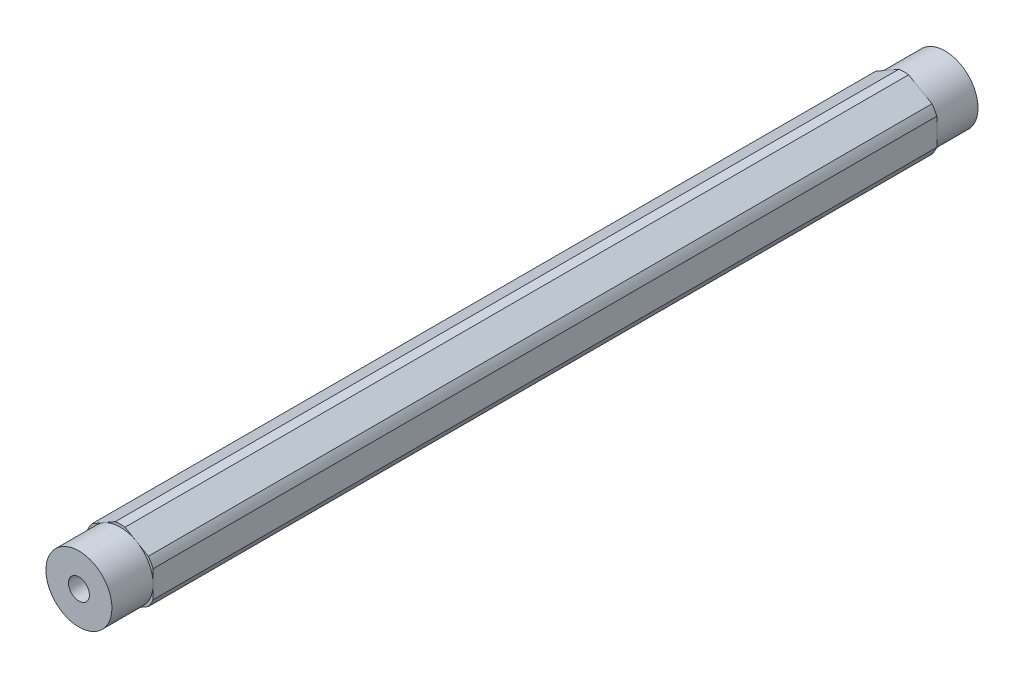
SolidWorks part; units mm, degrees
ref_plane "Front Plane" through (0, 0, 0) normal (0, 0, 1) x (1, 0, 0)
ref_plane "Top Plane" through (0, 0, 0) normal (0, 1, 0) x (1, 0, 0)
ref_plane "Right Plane" through (0, 0, 0) normal (1, 0, 0) x (0, 0, -1)
sketch "Sketch1" plane through (0, 0, 0) normal (0, 0, 1) x (1, 0, 0)
  line L1 (0, 7.3323) -> (-6.35, 3.6662)
  line L2 (-6.35, 3.6662) -> (-6.35, -3.6662)
  line L3 (-6.35, -3.6662) -> (0, -7.3323)
  line L4 (0, -7.3323) -> (6.35, -3.6662)
  line L5 (6.35, -3.6662) -> (6.35, 3.6662)
  line L6 (6.35, 3.6662) -> (0, 7.3323)
  circle A0 centre (0, 0) radius 6.35 construction
  circle A1 centre (0, 0) radius 6.858
  circle A2 centre (0, 0) radius 2.0193
  dimension "D1" = 12.7
  dimension "D2" = 13.716
  dimension "D3" = 4.0386
extrude "Boss-Extrude1" add sketch "Sketch1" along normal mid plane 150.8125 contours L5 A1 L6 L1 L2 L3 L4 region at (0, 6.6711, 0)
sketch "Sketch2" plane through (0, 0, 75.4062) normal (0, 0, 1) x (1, 0, 0)
  circle A0 centre (0, 0) radius 6.35
  circle A1 centre (0, 0) radius 2.0193
  dimension "D1" = 12.7
  dimension "D2" = 4.0386
extrude "Boss-Extrude2" add sketch "Sketch2" along normal blind 7.9375
mirror "Mirror1" about plane through (0, 0, 0) normal (0, 0, 1) of "Boss-Extrude2"
